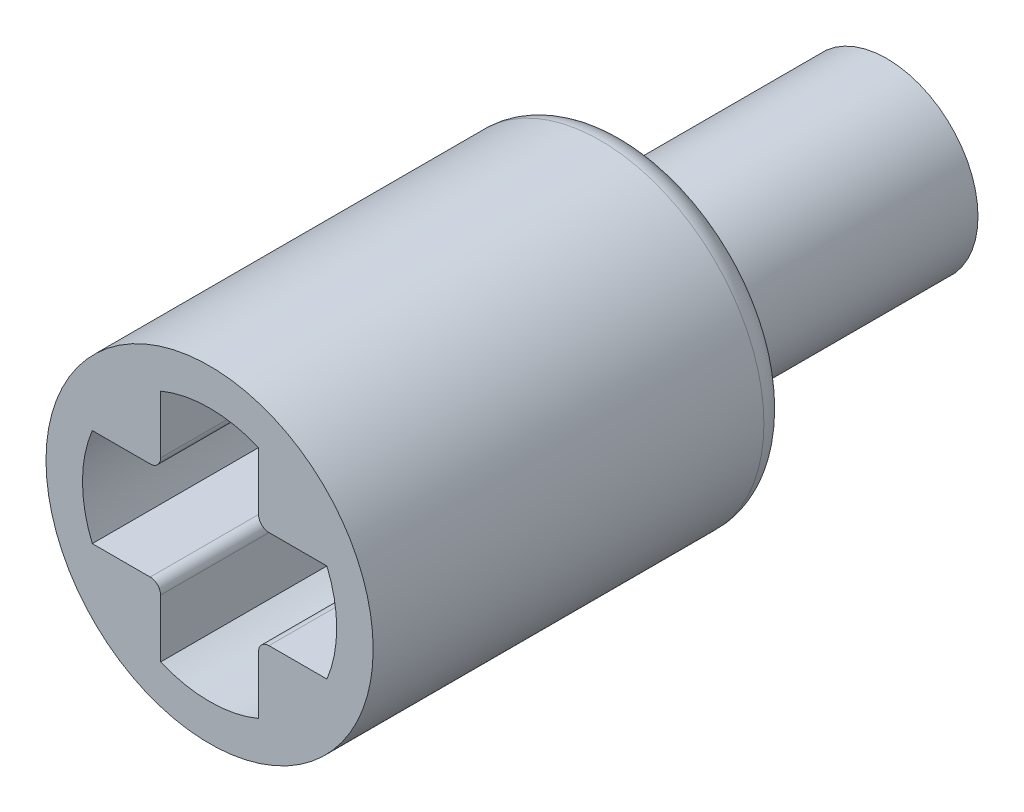
SolidWorks part; units mm, degrees
ref_plane "Front Plane" through (0, 0, 0) normal (0, 0, 1) x (1, 0, 0)
ref_plane "Top Plane" through (0, 0, 0) normal (0, 1, 0) x (1, 0, 0)
ref_plane "Right Plane" through (0, 0, 0) normal (1, 0, 0) x (0, 0, -1)
sketch "Sketch1" plane through (0, 0, 0) normal (0, 0, 1) x (1, 0, 0)
  circle A0 centre (0, 0) radius 1
  circle A1 centre (0, 0) radius 1.75
  dimension "D1" = 2
  dimension "D2" = 0.75
extrude "Boss-Extrude1" add sketch "Sketch1" along normal blind 5
sketch "Sketch2" plane through (0, 0, 5) normal (0, 0, 1) x (1, 0, 0)
  line L0 (0.89, 0.89) -> (0.89, 2.2181) construction
  line L1 (0.89, 0.89) -> (2.2181, 0.89) construction
  line L2 (2.2181, -0.89) -> (0.89, -0.89) construction
  line L3 (0.89, -0.89) -> (0.89, -2.2181) construction
  line L4 (-0.89, -2.2181) -> (-0.89, -0.89) construction
  line L5 (-0.89, -0.89) -> (-2.2181, -0.89) construction
  line L6 (-2.2181, 0.89) -> (-0.89, 0.89) construction
  line L7 (-0.89, 0.89) -> (-0.89, 2.2181) construction
  line L8 (0.94, 0.94) -> (2.2517, 0.94)
  line L9 (0.94, 0.94) -> (0.94, 2.2517)
  line L10 (-0.94, 0.94) -> (-0.94, 2.2517)
  line L11 (-2.2517, 0.94) -> (-0.94, 0.94)
  line L12 (-0.94, -0.94) -> (-2.2517, -0.94)
  line L13 (-0.94, -2.2517) -> (-0.94, -0.94)
  line L14 (0.94, -0.94) -> (0.94, -2.2517)
  line L15 (2.2517, -0.94) -> (0.94, -0.94)
  circle A0 centre (0, 0) radius 3.14
  circle A1 centre (0, 0) radius 1.75
  circle A2 centre (0, 0) radius 1.75
  arc A3 (-0.89, 2.2181) -> (0.89, 2.2181) centre (0, 0) cw construction
  arc A4 (-2.2181, 0.89) -> (-2.2181, -0.89) centre (0, 0) ccw construction
  arc A5 (-0.89, -2.2181) -> (0.89, -2.2181) centre (0, 0) ccw construction
  arc A6 (2.2181, -0.89) -> (2.2181, 0.89) centre (0, 0) ccw construction
  arc A7 (2.2517, -0.94) -> (2.2517, 0.94) centre (0, 0) ccw
  arc A8 (-0.94, 2.2517) -> (0.94, 2.2517) centre (0, 0) cw
  arc A9 (-2.2517, 0.94) -> (-2.2517, -0.94) centre (0, 0) ccw
  arc A10 (-0.94, -2.2517) -> (0.94, -2.2517) centre (0, 0) ccw
  line B0 (-0.89, 2.2181) -> (-0.89, 0.89) construction
  line B1 (-0.89, 0.89) -> (-2.2181, 0.89) construction
  line B2 (0.89, 2.2181) -> (0.89, 0.89) construction
  line B3 (0.89, 0.89) -> (2.2181, 0.89) construction
  line B4 (-2.2181, -0.89) -> (-0.89, -0.89) construction
  line B5 (-0.89, -0.89) -> (-0.89, -2.2181) construction
  line B6 (0.89, -2.2181) -> (0.89, -0.89) construction
  line B7 (0.89, -0.89) -> (2.2181, -0.89) construction
  arc B8 (-0.89, 2.2181) -> (0.89, 2.2181) centre (0, 0) cw construction
  arc B9 (-2.2181, 0.89) -> (-2.2181, -0.89) centre (0, 0) ccw construction
  arc B10 (2.2181, 0.89) -> (2.2181, -0.89) centre (0, 0) cw construction
  arc B11 (-0.89, -2.2181) -> (0.89, -2.2181) centre (0, 0) ccw construction
  circle M23 centre (0, 0) radius 1.75
  circle M24 centre (0, 0) radius 1
  dimension "D2" = 0.75
  dimension "D1" = 0
  dimension "D3" = 0.05
sketch_block_instance "Lego Axle - Unfilleted-1"
sketch_block "Lego Axle - Unfilleted"
extrude "Boss-Extrude2" add sketch "Sketch2" along normal blind 1 contours A0 A10 L13 L12 A9 L11 L10 A8 L9 L8 A7 L15 L14 M23 | L11 L10 M23 | L11 A9 L12 M23 | L15 L8 L9 L10 L11 L12 L13 L14 M23 M24 | M24 | A8 L10 L9 M23 | L9 L8 M23 | L15 A7 L8 M23 | L15 L14 M23 | L13 A10 L14 M23 | L13 L12 M23 region at (1.1316, 1.1316, 5) region at (1.2081, 0.8905, 5) region at (2.0176, 0, 5) region at (0, 2.0176, 5) region at (-1.1316, 1.1316, 5) region at (1.1316, -1.1316, 5) region at (-2.0176, 0, 5) region at (0, -2.0176, 5) region at (-1.1316, -1.1316, 5) region at (-3.0512, 0, 5) region at (0, 0, 5)
extrude "Boss-Extrude3" add sketch "Sketch2<4>" along normal blind 8 contours A0 A10 L13 L12 A9 L11 L10 A8 L9 L8 A7 L15 L14 M23 | L11 L10 M23 | L9 L8 M23 | L15 L14 M23 | L13 L12 M23 region at (1.1316, 1.1316, 5) region at (-1.1316, 1.1316, 5) region at (1.1316, -1.1316, 5) region at (-1.1316, -1.1316, 5) region at (-3.0512, 0, 5)
sketch "Sketch2<4>" plane through (0, 0, 5) normal (0, 0, 1) x (1, 0, 0) same geometry as "Sketch2"
fillet "Fillet1" radius 0.5 2 edges at (3.14, 0, 5) (1.75, 0, 5)
fillet "Fillet2" radius 0.2 4 edges at (-0.94, 0.94, 9.5) (0.94, 0.94, 9.5) (0.94, -0.94, 9.5) (-0.94, -0.94, 9.5)
